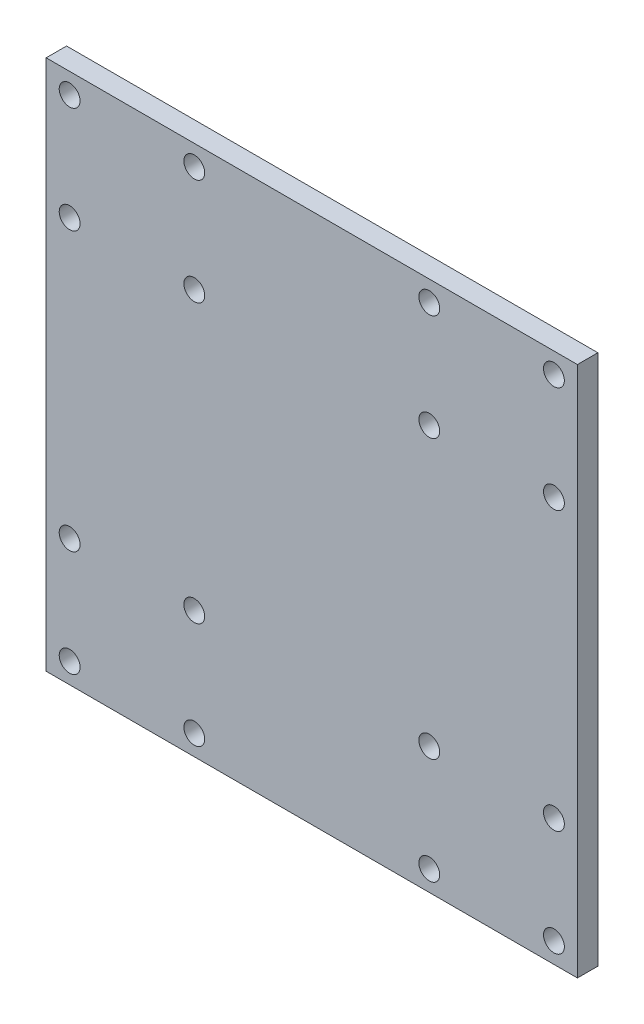
SolidWorks part; units mm, degrees
ref_plane "Front Plane" through (0, 0, 0) normal (0, 0, 1) x (1, 0, 0)
ref_plane "Top Plane" through (0, 0, 0) normal (0, 1, 0) x (1, 0, 0)
ref_plane "Right Plane" through (0, 0, 0) normal (1, 0, 0) x (0, 0, -1)
sketch "Sketch1" plane through (0, 0, 0) normal (0, 0, 1) x (1, 0, 0)
  line L1 (-65, -65) -> (65, -65)
  line L2 (-65, -65) -> (-65, 65)
  line L3 (-65, 65) -> (65, 65)
  line L4 (65, -65) -> (65, 65)
  line L5 (-65, -65) -> (65, 65) construction
  line L6 (-65, 65) -> (65, -65) construction
  point P0 (0, 0)
  dimension "D1" = 130
  dimension "D2" = 130
extrude "Boss-Extrude1" add sketch "Sketch1" along normal mid plane 5
sketch "Sketch2" plane through (0, 0, 2.5) normal (0, 0, 1) x (1, 0, 0)
  line L3 (-59.25, 65) -> (-59.25, -65)
  line L4 (-59.25, 65) -> (-59.25, -65) construction
  line L6 (59.25, -65) -> (59.25, 65)
  line L7 (59.25, -65) -> (59.25, 65) construction
  line L13 (-28.75, 65) -> (-28.75, -65)
  line L14 (-28.75, 65) -> (-28.75, -65) construction
  line L16 (28.75, -65) -> (28.75, 65)
  line L18 (28.75, -65) -> (28.75, 65) construction
  line L20 (65, 60) -> (-65, 60)
  line L21 (65, 60) -> (-65, 60) construction
  line L23 (-65, -60) -> (65, -60)
  line L24 (-65, -60) -> (65, -60) construction
  line L26 (65, 34) -> (-65, 34)
  line L27 (65, 34) -> (-65, 34) construction
  line L29 (-65, -34) -> (65, -34)
  line L30 (-65, -34) -> (65, -34) construction
  circle A0 centre (-59.25, 60) radius 2.55
  circle A1 centre (-28.75, 60) radius 2.55
  circle A2 centre (-28.75, 34) radius 2.55
  circle A3 centre (-59.25, 34) radius 2.55
  circle A4 centre (59.25, 60) radius 2.55
  circle A5 centre (59.25, 34) radius 2.55
  circle A6 centre (28.75, 34) radius 2.55
  circle A7 centre (28.75, 60) radius 2.55
  circle A8 centre (-59.25, -34) radius 2.55
  circle A9 centre (-28.75, -34) radius 2.55
  circle A10 centre (-28.75, -60) radius 2.55
  circle A11 centre (-59.25, -60) radius 2.55
  circle A12 centre (28.75, -34) radius 2.55
  circle A13 centre (59.25, -34) radius 2.55
  circle A14 centre (59.25, -60) radius 2.55
  circle A15 centre (28.75, -60) radius 2.55
  dimension "D9" = 5.1
  dimension "D10" = 5.1
  dimension "D11" = 5.1
  dimension "D12" = 5.1
  dimension "D13" = 5.1
  dimension "D14" = 5.1
  dimension "D15" = 5.1
  dimension "D16" = 5.1
  dimension "D17" = 5.1
  dimension "D18" = 5.1
  dimension "D19" = 5.1
  dimension "D20" = 5.1
  dimension "D21" = 5.1
  dimension "D22" = 5.1
  dimension "D23" = 5.1
  dimension "D24" = 5.1
  dimension "D1" = 5.75
  dimension "D2" = 5.75
  dimension "D3" = 36.25
  dimension "D4" = 36.25
  dimension "D5" = 5
  dimension "D6" = 5
  dimension "D7" = 31
  dimension "D8" = 31
extrude "Cut-Extrude1" cut sketch "Sketch2" against normal through all
